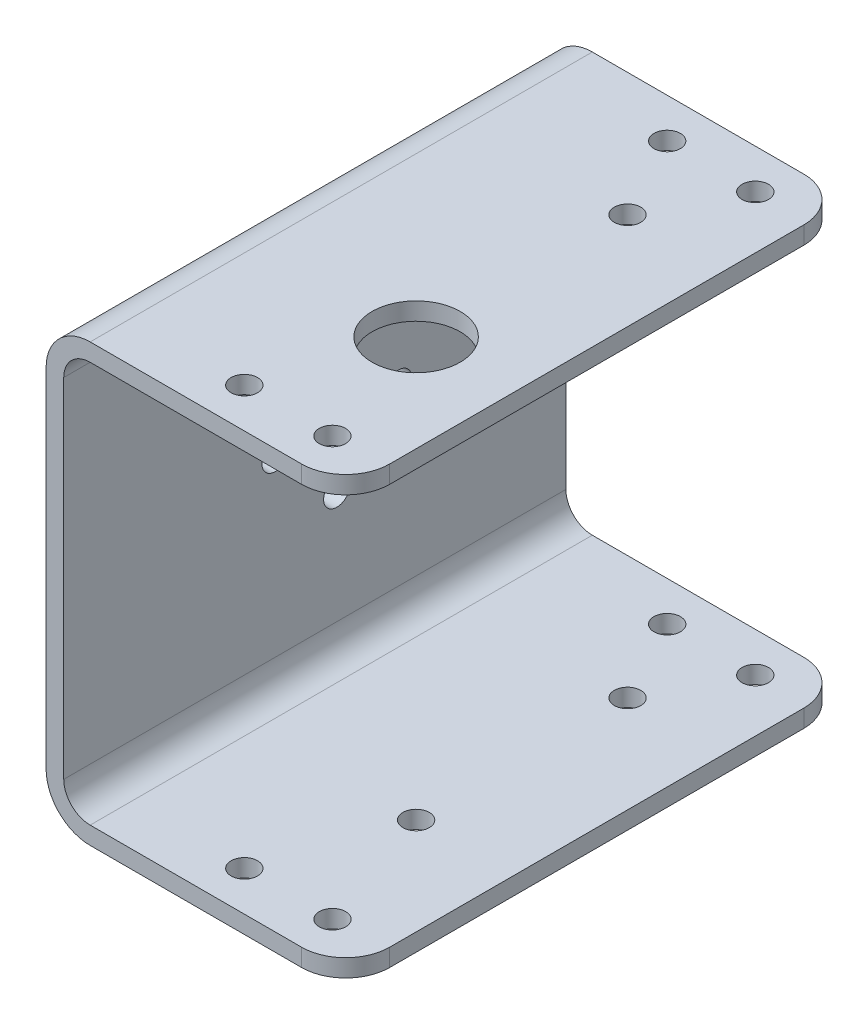
SolidWorks part; units mm, degrees
ref_plane "前视基准面" through (0, 0, 0) normal (0, 0, 1) x (1, 0, 0)
ref_plane "上视基准面" through (0, 0, 0) normal (0, 1, 0) x (1, 0, 0)
ref_plane "右视基准面" through (0, 0, 0) normal (1, 0, 0) x (0, 0, -1)
sketch "草图1" plane through (0, 0, 0) normal (0, 0, 1) x (1, 0, 0)
  line L1 (-17, -24.75) -> (17, -24.75)
  line L2 (-17, -24.75) -> (-17, 24.75)
  line L3 (-17, 24.75) -> (17, 24.75)
  line L4 (17, -24.75) -> (17, -22.75)
  line L7 (-15, -22.75) -> (-15, 22.75)
  line L8 (15, -22.75) -> (15, 22.75) construction
  line L9 (-15, 22.75) -> (15, 22.75) construction
  line L10 (-15, -22.75) -> (15, -22.75) construction
  line L11 (-15, 22.75) -> (17, 22.75)
  line L12 (-15, -22.75) -> (17, -22.75)
  line L13 (17, 22.75) -> (17, 24.75)
  line L15 (17, -24.75) -> (17, 24.75) construction
  point P0 (0, 0)
extrude "凸台-拉伸1" add sketch "草图1" along normal blind 57
sketch "草图2" plane through (0, 24.75, 0) normal (0, 1, 0) x (1, 0, 0)
  line L0 (17, 0) -> (-17, 0) construction
  circle A0 centre (6, -14) radius 1.5
  circle A1 centre (6, -38) radius 1.5
extrude "切除-拉伸1" cut sketch "草图2" against normal blind 57
sketch "草图4" plane through (-17, 0, 0) normal (-1, 0, 0) x (0, 0, 1)
  circle A0 centre (26, 0) radius 4
  circle A1 centre (26, 7) radius 1.5
  circle A2 centre (33, 0) radius 1.5
  circle A3 centre (26, -7) radius 1.5
  circle A4 centre (19, 0) radius 1.5
  point P13 (26, 0)
  dimension "D1" = 4
extrude "切除-拉伸2" cut sketch "草图4" against normal blind 57
fillet "圆角1" radius 5 2 edges at (-17, -24.75, 28.5) (-17, 24.75, 28.5)
fillet "圆角2" radius 3 2 edges at (-15, -22.75, 28.5) (-15, 22.75, 28.5)
fillet "圆角3" radius 5 4 edges at (17, 23.75, 0) (17, -23.75, 0) (17, 23.75, 57) (17, -23.75, 57)
sketch "草图5" plane through (0, 24.75, 0) normal (0, 1, 0) x (1, 0, 0)
  circle A0 centre (6, -38) radius 5
extrude "切除-拉伸3" cut sketch "草图5" against normal blind 26
sketch "草图6" plane through (0, -24.75, 0) normal (0, -1, 0) x (1, 0, 0)
  circle A0 centre (1, 52.5) radius 1.5
  circle A1 centre (11, 52.5) radius 1.5
  circle A2 centre (11, 4.5) radius 1.5
  circle A3 centre (1, 4.5) radius 1.5
extrude "切除-拉伸4" cut sketch "草图6" against normal blind 71
